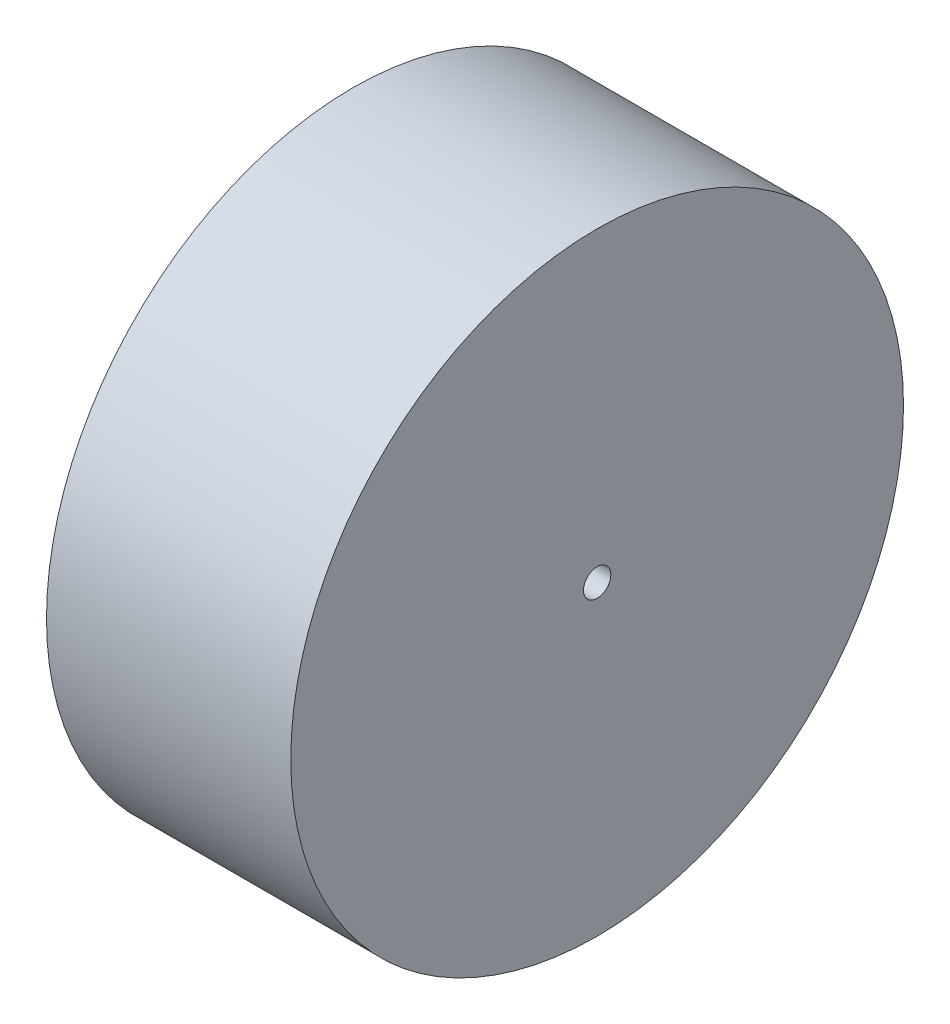
SolidWorks part; units mm, degrees
ref_plane "Plan de face" through (0, 0, 0) normal (0, 0, 1) x (1, 0, 0)
ref_plane "Plan de dessus" through (0, 0, 0) normal (0, 1, 0) x (1, 0, 0)
ref_plane "Plan de droite" through (0, 0, 0) normal (1, 0, 0) x (0, 0, -1)
sketch "Esquisse1" plane through (0, 0, 0) normal (1, 0, 0) x (0, 0, -1)
  circle A0 centre (0, 0) radius 32.735
  circle A1 centre (0, 0) radius 1.46
extrude "Boss.-Extru.4" add sketch "Esquisse1" along normal blind 13.05 and the other way blind 13.05
